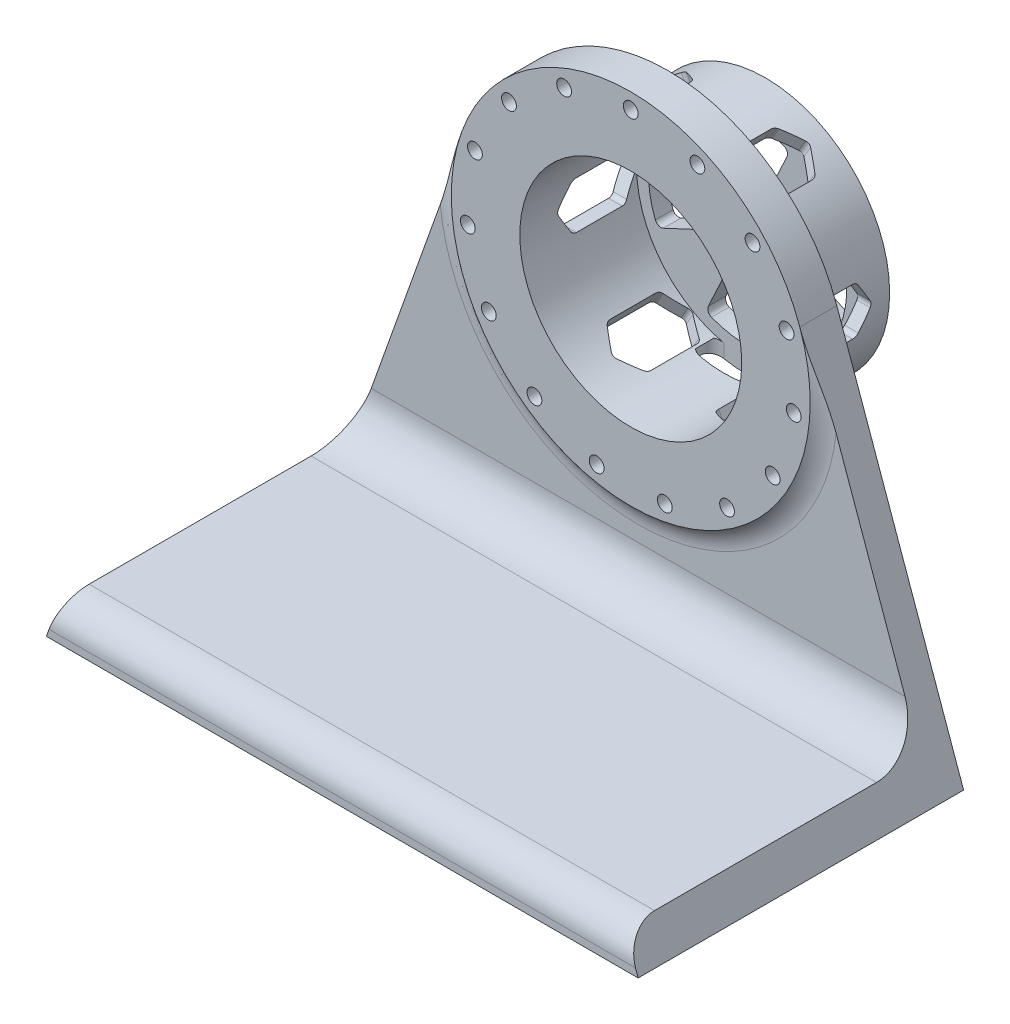
SolidWorks part; units mm, degrees
ref_plane "Front Plane" through (0, 0, 0) normal (0, 0, 1) x (1, 0, 0)
ref_plane "Top Plane" through (0, 0, 0) normal (0, 1, 0) x (1, 0, 0)
ref_plane "Right Plane" through (0, 0, 0) normal (1, 0, 0) x (0, 0, -1)
sketch "Sketch1" plane through (0, 0, 0) normal (0, 0, 1) x (1, 0, 0)
  line L0 (-57.1341, 20.3499) -> (-100, -100)
  line L1 (-100, -100) -> (100, -100)
  line L2 (0, -100) -> (0, 0) construction
  line L3 (57.1341, 20.3499) -> (100, -100)
  arc A0 (57.1341, 20.3499) -> (-57.1341, 20.3499) centre (0, 0) ccw
  circle A1 centre (0, 0) radius 55.375 construction
  circle A2 centre (0, 55.375) radius 2.5
  circle A3 centre (22.523, 50.5876) radius 2.5
  circle A4 centre (41.1516, 37.0531) radius 2.5
  circle A5 centre (52.6648, 17.1118) radius 2.5
  circle A6 centre (55.0716, -5.7883) radius 2.5
  circle A7 centre (47.9562, -27.6875) radius 2.5
  circle A8 centre (32.5486, -44.7993) radius 2.5
  circle A9 centre (11.5131, -54.1649) radius 2.5
  circle A10 centre (-11.5131, -54.1649) radius 2.5
  circle A11 centre (-32.5486, -44.7993) radius 2.5
  circle A12 centre (-47.9562, -27.6875) radius 2.5
  circle A13 centre (-55.0716, -5.7883) radius 2.5
  circle A14 centre (-52.6648, 17.1118) radius 2.5
  circle A15 centre (-41.1516, 37.0531) radius 2.5
  circle A16 centre (-22.523, 50.5876) radius 2.5
  circle A17 centre (0, 0) radius 37.5
  dimension "D1" = 121.3
  dimension "D2" = 110.75
  dimension "D3" = 5
  dimension "D7" = 75
  dimension "D5" = 100
  dimension "D6" = 100
  dimension "D4" = 15
extrude "Boss-Extrude1" add sketch "Sketch1" along normal blind 10
sketch "Sketch2" plane through (0, 0, 10) normal (0, 0, 1) x (1, 0, 0)
  line L0 (-95.5478, -87.5) -> (95.5478, -87.5)
  line L3 (-57.1341, 20.3499) -> (-100, -100)
  line L4 (-100, -100) -> (100, -100)
  line L5 (100, -100) -> (57.1341, 20.3499)
  line L6 (-95.5478, -87.5) -> (-100, -100)
  line L7 (-100, -100) -> (100, -100)
  line L8 (100, -100) -> (95.5478, -87.5)
  arc A1 (57.1341, 20.3499) -> (-57.1341, 20.3499) centre (0, 0) ccw
  dimension "D2" = 12.5
  dimension "D1" = 0
extrude "Boss-Extrude2" add sketch "Sketch2" along normal blind 100
fillet "Fillet1" radius 15 1 edges at (0, -87.5, 10)
sketch "Sketch3" plane through (0, 0, 0) normal (0, 0, -1) x (-1, 0, 0)
  circle A0 centre (0, 0) radius 42
  circle A1 centre (0, 0) radius 37.5 construction
  circle A2 centre (0, 0) radius 37.5
  dimension "D1" = 4.5
extrude "Boss-Extrude3" add sketch "Sketch3" along normal blind 27
sketch "Sketch4" plane through (0, 0, -27) normal (0, 0, -1) x (-1, 0, 0)
  line L0 (0, 0) -> (15, 0) construction
  line L1 (0, 0) -> (10.6066, 10.6066) construction
  circle A0 centre (0, 0) radius 42 construction
  circle A1 centre (0, 0) radius 42
  circle A2 centre (0, 0) radius 10
  circle A3 centre (0, 0) radius 15 construction
  circle A4 centre (10.6066, 10.6066) radius 2.1
  circle A5 centre (10.6066, -10.6066) radius 2.1
  circle A6 centre (-10.6066, -10.6066) radius 2.1
  circle A7 centre (-10.6066, 10.6066) radius 2.1
  dimension "D1" = 20
  dimension "D2" = 30
  dimension "D3" = 45
  dimension "D4" = 4.2
  dimension "D5" = 4
extrude "Boss-Extrude4" add sketch "Sketch4" along normal blind 6
ref_plane "Plane2" through (0, -42, 0) normal (0, -1, 0) x (-1, 0, 0)
sketch "Sketch5" plane through (0, -42, 0) normal (0, -1, 0) x (-1, 0, 0)
  line L0 (0, 33) -> (0, 27) construction
  line L1 (42, 33) -> (-42, 33) construction
  line L2 (0, 27) -> (0, 23) construction
  line L3 (-8, 23) -> (8, 23) construction
  line L4 (-8, 27) -> (8, 27)
  line L5 (-8, 19) -> (8, 19)
  arc A0 (-8, 27) -> (-8, 19) centre (-8, 23) ccw
  arc A1 (8, 19) -> (8, 27) centre (8, 23) ccw
  point P8 (0, 23)
  dimension "D1" = 6
  dimension "D2" = 4
  dimension "D3" = 8
extrude "Cut-Extrude1" cut sketch "Sketch5" against normal blind 6
sketch "Sketch6" plane through (0, 0, -33) normal (0, 0, -1) x (-1, 0, 0)
  line L1 (-26, -28) -> (26, -28) construction
  line L2 (-26, -28) -> (-26, 28) construction
  line L3 (-26, 28) -> (26, 28) construction
  line L4 (26, -28) -> (26, 28) construction
  line L5 (-26, -28) -> (26, 28) construction
  line L6 (-26, 28) -> (26, -28) construction
  circle A0 centre (-26, 28) radius 2.5
  circle A1 centre (26, 28) radius 2.5
  circle A2 centre (26, -28) radius 2.5
  circle A3 centre (-26, -28) radius 2.5
  point P0 (0, 0)
  dimension "D3" = 5
  dimension "D1" = 56
  dimension "D2" = 52
extrude "Cut-Extrude2" cut sketch "Sketch6" against normal blind 5
fillet "Fillet2" radius 10 1 edges at (0, -87.5, 110)
ref_plane "Plane3" through (-42, 0, 0) normal (-1, 0, 0) x (0, 0, 1)
sketch "Sketch7" plane through (-42, 0, 0) normal (-1, 0, 0) x (0, 0, 1)
  line L0 (0, 0) -> (-33, 0) construction
  line L1 (-33, 42) -> (-33, -42) construction
  line L2 (-4.6188, 8) -> (-22.3812, 8)
  line L3 (-22.3812, 8) -> (-27, 0)
  line L4 (-4.6188, 8) -> (0, 0)
  line L5 (-4.6188, -8) -> (0, 0)
  line L6 (-4.6188, -8) -> (-22.3812, -8)
  line L7 (-22.3812, -8) -> (-27, 0)
  dimension "D1" = 8
  dimension "D2" = 120
  dimension "D3" = 120
  dimension "D4" = 6
extrude "Cut-Extrude3" cut sketch "Sketch7" against normal blind 10
fillet "Fillet3" radius 2 6 edges at (-38.9339, -8, -4.6188) (-38.9339, -8, -22.3812) (-39.75, 0, -27) (-38.9339, 8, -22.3812) (-38.9339, 8, -4.6188) (-39.75, 0, 0)
pattern_circular "CirPattern1" count 6 over 360 about axis through (0, 0, -33) along (0, 0, -1) of "Cut-Extrude3", "Fillet3"
sketch "Sketch8" plane through (0, 0, -33) normal (0, 0, -1) x (-1, 0, 0)
  line L0 (0, 0) -> (-14.1577, 30.3613)
  line L1 (0, 0) -> (14.1577, 30.3613)
  line L2 (0, 0) -> (0, 33.5) construction
  line L3 (0, 0) -> (30.3613, -14.1577)
  line L4 (0, 0) -> (30.3613, 14.1577)
  line L5 (0, 0) -> (-14.1577, -30.3613)
  line L6 (0, 0) -> (14.1577, -30.3613)
  line L7 (0, 0) -> (-30.3613, 14.1577)
  line L8 (0, 0) -> (-30.3613, -14.1577)
  arc A0 (-30.3613, 14.1577) -> (-30.3613, -14.1577) centre (0, 0) ccw
  arc A1 (-14.1577, -30.3613) -> (14.1577, -30.3613) centre (0, 0) ccw
  arc A2 (30.3613, -14.1577) -> (30.3613, 14.1577) centre (0, 0) ccw
  arc A3 (14.1577, 30.3613) -> (-14.1577, 30.3613) centre (0, 0) ccw
  circle M11 centre (0, 0) radius 10
  dimension "D1" = 67
  dimension "D2" = 50
  dimension "D3" = 25
  dimension "D4" = 4
extrude "Cut-Extrude4" cut sketch "Sketch8" against normal blind 10 contours L3 A2 L4 M11 | L2 L1 A3 M11 | L7 A0 L8 M11 | L5 A1 L6 M11 | L0 A3 L1 region at (-5.1246, 23.1158, -33) region at (-23.1158, 0, -33) region at (0, -23.1158, -33) region at (23.1158, 0, -33)
fillet "Fillet4" radius 2 16 edges at (-30.3613, -14.1577, -30) (-9.0631, -4.2262, -30) (-4.2262, -9.0631, -30) (-14.1577, -30.3613, -30) (14.1577, -30.3613, -30) (4.2262, -9.0631, -30) (9.0631, -4.2262, -30) (30.3613, -14.1577, -30) (30.3613, 14.1577, -30) (9.0631, 4.2262, -30) (-14.1577, 30.3613, -30) (-30.3613, 14.1577, -30) (-4.2262, 9.0631, -30) (-9.0631, 4.2262, -30) (4.2262, 9.0631, -30) (14.1577, 30.3613, -30)
chamfer "Chamfer1" distance 1 angle 45 4 edges at (8.5066, -10.6066, -33) (-12.7066, -10.6066, -33) (-12.7066, 10.6066, -33) (8.5066, 10.6066, -33)
sketch "Sketch9" plane through (0, 0, 10) normal (0, 0, 1) x (1, 0, 0)
  line L3 (-57.1341, 20.3499) -> (-90.2051, -72.5)
  line L4 (-90.2051, -72.5) -> (90.2051, -72.5)
  line L5 (90.2051, -72.5) -> (57.1341, 20.3499)
  circle A0 centre (0, 0) radius 60.65
  arc A1 (57.1341, 20.3499) -> (-57.1341, 20.3499) centre (0, 0) ccw
  arc A2 (57.1341, 20.3499) -> (-57.1341, 20.3499) centre (0, 0) ccw
  circle A5 centre (0, 0) radius 37.5 construction
  circle A6 centre (11.5131, -54.1649) radius 2.5 construction
  circle A7 centre (0, 0) radius 37.5
  circle A8 centre (11.5131, -54.1649) radius 2.5
  circle A9 centre (-11.5131, -54.1649) radius 2.5
  circle A10 centre (-32.5486, -44.7993) radius 2.5
  circle A11 centre (-47.9562, -27.6875) radius 2.5
  circle A12 centre (-55.0716, -5.7883) radius 2.5
  circle A13 centre (-52.6648, 17.1118) radius 2.5
  circle A14 centre (-41.1516, 37.0531) radius 2.5
  circle A15 centre (-22.523, 50.5876) radius 2.5
  circle A16 centre (0, 55.375) radius 2.5
  circle A17 centre (22.523, 50.5876) radius 2.5
  circle A18 centre (41.1516, 37.0531) radius 2.5
  circle A19 centre (52.6648, 17.1118) radius 2.5
  circle A20 centre (55.0716, -5.7883) radius 2.5
  circle A21 centre (47.9562, -27.6875) radius 2.5
  circle A22 centre (32.5486, -44.7993) radius 2.5
  arc M9 (57.1341, 20.3499) -> (-57.1341, 20.3499) centre (0, 0) ccw
  circle M10 centre (-41.1516, 37.0531) radius 2.5
  circle M11 centre (-55.0716, -5.7883) radius 2.5
  circle M12 centre (-32.5486, -44.7993) radius 2.5
  circle M13 centre (11.5131, -54.1649) radius 2.5
  circle M14 centre (47.9562, -27.6875) radius 2.5
  circle M15 centre (52.6648, 17.1118) radius 2.5
  circle M16 centre (22.523, 50.5876) radius 2.5
  circle M17 centre (0, 0) radius 37.5
  circle M18 centre (0, 55.375) radius 2.5
  circle M19 centre (41.1516, 37.0531) radius 2.5
  circle M20 centre (55.0716, -5.7883) radius 2.5
  circle M21 centre (32.5486, -44.7993) radius 2.5
  circle M22 centre (-11.5131, -54.1649) radius 2.5
  circle M23 centre (-47.9562, -27.6875) radius 2.5
  circle M24 centre (-52.6648, 17.1118) radius 2.5
  circle M25 centre (-22.523, 50.5876) radius 2.5
  dimension "D2" = 15
  dimension "D1" = 0
extrude "Boss-Extrude5" add sketch "Sketch9" along normal blind 2.5 contours A0 M9 M10 M12 M14 M16 M18 M20 M22 M24 M25 M23 M21 M19 M17 M15 M13 M11 region at (0, 58.9346, 10)
fillet "Fillet5" radius 10 1 edges at (0, -60.65, 10)
sketch "Sketch10" plane through (0, -100, 0) normal (0, 0, 1) x (1, 0, 0)
  line L0 (-100, 6.25) -> (100, 6.25) construction
  line L3 (-100, 0) -> (100, 0) construction
  line L4 (0, 0) -> (0, 6.25) construction
  circle A0 centre (-90, 6.25) radius 1.375
  circle A1 centre (-70, 6.25) radius 1.375
  circle A2 centre (-50, 6.25) radius 1.375
  circle A3 centre (-30, 6.25) radius 1.375
  circle A4 centre (-10, 6.25) radius 1.375
  circle A5 centre (10, 6.25) radius 1.375
  circle A6 centre (30, 6.25) radius 1.375
  circle A7 centre (50, 6.25) radius 1.375
  circle A8 centre (70, 6.25) radius 1.375
  circle A9 centre (90, 6.25) radius 1.375
  point P4 (0, 0)
  point P5 (0, 0)
  dimension "D2" = 2.75
  dimension "D4" = 10
  dimension "D6" = 10
  dimension "D1" = 6.25
  dimension "D3" = 200
  dimension "D5" = 20
extrude "Cut-Extrude5" cut sketch "Sketch10" along normal blind 30
